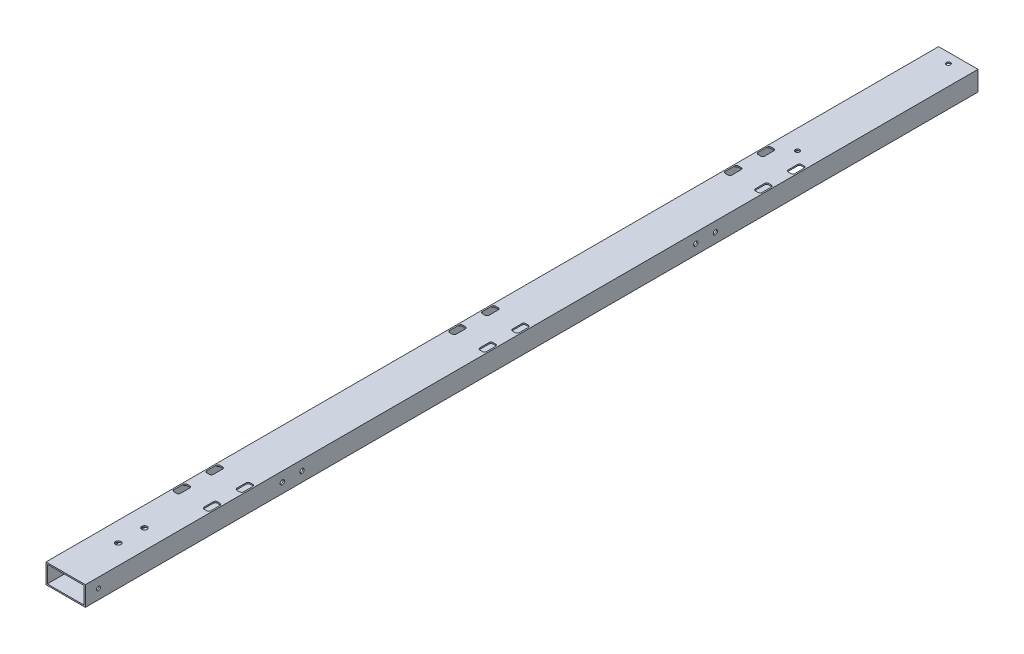
SolidWorks part; units mm, degrees
material "1060 合金"
ref_plane "前视基准面" through (0, 0, 0) normal (0, 0, 1) x (1, 0, 0)
ref_plane "上视基准面" through (0, 0, 0) normal (0, 1, 0) x (1, 0, 0)
ref_plane "右视基准面" through (0, 0, 0) normal (1, 0, 0) x (0, 0, -1)
other "Configuration Table"
sketch "草图1" plane through (0, 0, 0) normal (0, 0, 1) x (1, 0, 0)
  line L1 (0, 0) -> (30, 0)
  line L2 (0, 0) -> (0, -15)
  line L3 (0, -15) -> (30, -15)
  line L4 (30, 0) -> (30, -15)
  dimension "D1" = 15
  dimension "D2" = 30
extrude "拉伸-薄壁1" add sketch "草图1" along normal blind 800 thin thin type one direction reverse wall 1
sketch "草图2" plane through (0, -15, 0) normal (0, -1, 0) x (1, 0, 0)
  circle A1 centre (7.5, 825) radius 2.6
  circle A2 centre (7.5, 825) radius 2.6
  dimension "D1" = 0
extrude "切除-拉伸1" [suppressed] cut sketch "草图2" against normal up to next
sketch "草图3" plane through (0, 0, 0) normal (-1, 0, 0) x (0, 0, 1)
  line L0 (800, 0) -> (0, 0) construction
  line L1 (0, 0) -> (0, -15) construction
  circle A0 centre (215, -7.5) radius 1.7
  circle A1 centre (170, -7.5) radius 1.7
  dimension "D1" = 3.4
  dimension "D2" = 3.4
  dimension "D3" = 45
  dimension "D4" = 7.5
  dimension "D5" = 7.5
  dimension "D6" = 170
sketch "草图4" plane through (30, 0, 0) normal (1, 0, 0) x (0, 0, -1)
  line L0 (-800, -15) -> (0, -15) construction
  line L1 (-800, -15) -> (-800, 0) construction
  circle A0 centre (-790, -7.5) radius 1.5
  dimension "D1" = 3
  dimension "D2" = 7.5
  dimension "D3" = 10
extrude "切除-拉伸3" cut sketch "草图4" against normal through all
sketch "草图5" plane through (30, 0, 0) normal (1, 0, 0) x (0, 0, -1)
  line L0 (-800, 0) -> (0, 0) construction
  line L1 (0, -15) -> (0, 0) construction
  line L2 (-800, -1) -> (-800, -14) construction
  circle A0 centre (-320, -7.5) radius 1.65
  circle A1 centre (-335, -7.5) radius 1.65
  circle A2 centre (-635, -7.5) radius 1.65
  circle A3 centre (-650, -7.5) radius 1.65
  dimension "D1" = 3.3
  dimension "D4" = 3.3
  dimension "D7" = 7.5
  dimension "D9" = 3.3
  dimension "D10" = 3.3
  dimension "D2" = 7.5
  dimension "D3" = 15
  dimension "D5" = 7.5
  dimension "D6" = 320
  dimension "D8" = 7.5
  dimension "D11" = 15
  dimension "D12" = 150
extrude "切除-拉伸4" cut sketch "草图5" against normal through all
sketch "草图6" plane through (0, 0, 0) normal (0, 0, -1) x (-1, 0, 0)
  line L4 (0, -15) -> (0, 0)
  line L5 (0, 0) -> (-30, 0)
  line L6 (-30, 0) -> (-30, -15)
  line L7 (-30, -15) -> (0, -15)
  line L8 (0, -15) -> (0, 0)
  line L9 (0, 0) -> (-30, 0)
  line L10 (-30, 0) -> (-30, -15)
  line L11 (-30, -15) -> (0, -15)
  dimension "D1" = 0
extrude "切除-拉伸5" cut sketch "草图6" against normal blind 300
sketch "草图7" [suppressed] plane through (0, 0, 0) normal (0, 1, 0) x (1, 0, 0)
  line L0 (15, -300) -> (15, -861.2957) construction
  line L1 (0, -300) -> (30, -300) construction
  line L2 (0, -550) -> (263.5539, -550) construction
  line L3 (0, -800) -> (0, -300) construction
  circle A0 centre (7.5, -545) radius 1.25
  circle A1 centre (22.5, -545) radius 1.25
  circle A2 centre (22.5, -555) radius 1.25
  circle A3 centre (7.5, -555) radius 1.25
  circle A4 centre (7.5, -405) radius 1.25
  circle A5 centre (22.5, -405) radius 1.25
  circle A6 centre (22.5, -415) radius 1.25
  circle A7 centre (7.5, -415) radius 1.25
  circle A8 centre (7.5, -685) radius 1.25
  circle A9 centre (22.5, -685) radius 1.25
  circle A10 centre (22.5, -695) radius 1.25
  circle A11 centre (7.5, -695) radius 1.25
  circle A12 centre (7.5, -545) radius 1.25
  circle A13 centre (22.5, -545) radius 1.25
  circle A14 centre (22.5, -555) radius 1.25
  circle A15 centre (7.5, -555) radius 1.25
  line M12 (0, -300) -> (0, -800)
  line M14 (30, -800) -> (30, -300)
  dimension "D1" = 2.5
  dimension "D3" = 15
  dimension "D4" = 10
  dimension "D2" = 250
  dimension "D6" = 135
  dimension "D5" = 2
extrude "切除-拉伸6" [suppressed] cut sketch "草图7" against normal blind 155 contours A4 M12 | A7 M12 | A5 M14 | A6 M14 | A1 M14 | A0 M12 | A2 M14 | A8 M12 | A11 M12 | A9 M14 | A10 M14 | A3
sketch "草图8" plane through (0, 0, 300) normal (0, 0, -1) x (-1, 0, 0)
  line L0 (-1, -14) -> (-1, -1) construction
  line L1 (-1, -1) -> (-29, -1) construction
  line L2 (-29, -1) -> (-29, -14) construction
  line L3 (-29, -14) -> (-1, -14) construction
  line L4 (-30, -15) -> (0, -15)
  line L5 (0, -15) -> (0, 0)
  line L6 (0, 0) -> (-30, 0)
  line L7 (-30, 0) -> (-30, -15)
  line L8 (-30, -15) -> (0, -15)
  line L9 (0, -15) -> (0, 0)
  line L10 (0, 0) -> (-30, 0)
  line L11 (-30, 0) -> (-30, -15)
  line L12 (-1, -14) -> (-1, -1)
  line L13 (-1, -1) -> (-29, -1)
  line L14 (-29, -1) -> (-29, -14)
  line L15 (-29, -14) -> (-1, -14)
  dimension "D1" = 0
extrude "凸台-拉伸1" add sketch "草图8" along normal blind 180
sketch "草图9" plane through (0, 0, 0) normal (0, 1, 0) x (1, 0, 0)
  line L0 (0, -800) -> (0, -120) construction
  line L1 (30, -800) -> (0, -800) construction
  circle A0 centre (15, -740) radius 2.05
  circle A1 centre (15, -760) radius 2.05
  dimension "D1" = 4.1
  dimension "D2" = 15
  dimension "D3" = 60
  dimension "D4" = 2
extrude "切除-拉伸7" cut sketch "草图9" against normal blind 10
sketch "草图10" plane through (0, -15, 0) normal (0, -1, 0) x (1, 0, 0)
  line L0 (15, 735) -> (15, 760) construction
  line L1 (8, 735) -> (8, 760)
  line L2 (22, 735) -> (22, 760)
  line L3 (0, 800) -> (0, 120) construction
  line L4 (0, 800) -> (30, 800) construction
  arc A0 (8, 735) -> (22, 735) centre (15, 735) ccw
  arc A1 (22, 760) -> (8, 760) centre (15, 760) ccw
  point P2 (15, 747.5)
  dimension "D3" = 7
  dimension "D1" = 25
  dimension "D2" = 15
  dimension "D4" = 40
extrude "切除-拉伸8" cut sketch "草图10" against normal blind 10
sketch "草图11" plane through (0, -15, 0) normal (0, -1, 0) x (1, 0, 0)
  line L0 (0, 800) -> (0, 120) construction
  line L1 (30, 120) -> (0, 120) construction
  circle A0 centre (15, 127.5) radius 1.6
  circle A1 centre (15, 242.5) radius 1.6
  dimension "D1" = 3.2
  dimension "D2" = 15
  dimension "D3" = 7.5
  dimension "D4" = 2
extrude "切除-拉伸9" cut sketch "草图11" against normal through all
sketch "草图12" plane through (0, -15, 0) normal (0, -1, 0) x (1, 0, 0)
  line L0 (15, 247) -> (15, 237) construction
  line L1 (22, 247) -> (22, 237)
  line L2 (8, 247) -> (8, 237)
  line L3 (30, 120) -> (0, 120) construction
  line L4 (30, 800) -> (30, 120) construction
  arc A0 (22, 247) -> (8, 247) centre (15, 247) ccw
  arc A1 (8, 237) -> (22, 237) centre (15, 237) ccw
  point P2 (15, 242)
  dimension "D1" = 7
  dimension "D2" = 117
  dimension "D3" = 10
  dimension "D4" = 15
extrude "切除-拉伸10" cut sketch "草图12" against normal up to next
sketch "草图13" plane through (0, -15, 0) normal (0, -1, 0) x (1, 0, 0)
  line L0 (30, 800) -> (30, 120) construction
  line L1 (0, 800) -> (30, 800) construction
  circle A0 centre (27.5, 700) radius 1.25
  circle A1 centre (2.5, 700) radius 1.25
  circle A2 centre (2.5, 675) radius 1.25
  circle A3 centre (27.5, 675) radius 1.25
  circle A4 centre (27.5, 465) radius 1.25
  circle A5 centre (27.5, 490) radius 1.25
  circle A6 centre (2.5, 490) radius 1.25
  circle A7 centre (2.5, 465) radius 1.25
  circle A8 centre (27.5, 255) radius 1.25
  circle A9 centre (27.5, 280) radius 1.25
  circle A10 centre (2.5, 280) radius 1.25
  circle A11 centre (2.5, 255) radius 1.25
  dimension "D1" = 2.5
  dimension "D2" = 2.5
  dimension "D3" = 100
  dimension "D4" = 2
  dimension "D5" = 2
  dimension "D6" = 3
extrude "切除-拉伸11" cut sketch "草图13" against normal through all
sketch "草图14" plane through (0, -15, 0) normal (0, -1, 0) x (1, 0, 0)
  line L0 (30, 800) -> (30, 120) construction
  line L1 (1, 705) -> (6, 705)
  line L2 (1, 705) -> (1, 695)
  line L3 (1, 670) -> (6, 670)
  line L4 (29, 705) -> (29, 695)
  line L5 (0, 800) -> (0, 120) construction
  line L6 (1, 495) -> (6, 495)
  line L7 (1, 695) -> (6, 695)
  line L8 (1, 695) -> (1, 705)
  line L9 (1, 705) -> (6, 705)
  line L10 (6, 695) -> (6, 705)
  line L11 (29, 705) -> (24, 705)
  line L12 (29, 705) -> (29, 695)
  line L13 (29, 695) -> (24, 695)
  line L14 (24, 705) -> (24, 695)
  line L15 (1, 680) -> (6, 680)
  line L16 (1, 680) -> (1, 670)
  line L17 (1, 670) -> (6, 670)
  line L18 (6, 680) -> (6, 670)
  line L19 (29, 670) -> (24, 670)
  line L20 (29, 670) -> (29, 680)
  line L21 (29, 680) -> (24, 680)
  line L22 (24, 670) -> (24, 680)
  line L23 (1, 495) -> (1, 485)
  line L24 (1, 460) -> (6, 460)
  line L25 (29, 495) -> (29, 485)
  line L26 (1, 485) -> (6, 485)
  line L27 (1, 485) -> (1, 495)
  line L28 (1, 495) -> (6, 495)
  line L29 (6, 485) -> (6, 495)
  line L30 (29, 495) -> (24, 495)
  line L31 (29, 495) -> (29, 485)
  line L32 (29, 485) -> (24, 485)
  line L33 (24, 495) -> (24, 485)
  line L34 (1, 470) -> (6, 470)
  line L35 (1, 470) -> (1, 460)
  line L36 (1, 460) -> (6, 460)
  line L37 (6, 470) -> (6, 460)
  line L38 (29, 460) -> (24, 460)
  line L39 (29, 460) -> (29, 470)
  line L40 (29, 470) -> (24, 470)
  line L41 (24, 460) -> (24, 470)
  line L42 (1, 285) -> (6, 285)
  line L43 (1, 285) -> (1, 275)
  line L44 (1, 250) -> (6, 250)
  line L45 (29, 285) -> (29, 275)
  line L46 (1, 275) -> (6, 275)
  line L47 (1, 275) -> (1, 285)
  line L48 (1, 285) -> (6, 285)
  line L49 (6, 275) -> (6, 285)
  line L50 (29, 285) -> (24, 285)
  line L51 (29, 285) -> (29, 275)
  line L52 (29, 275) -> (24, 275)
  line L53 (24, 285) -> (24, 275)
  line L54 (1, 260) -> (6, 260)
  line L55 (1, 260) -> (1, 250)
  line L56 (1, 250) -> (6, 250)
  line L57 (6, 260) -> (6, 250)
  line L58 (29, 250) -> (24, 250)
  line L59 (29, 250) -> (29, 260)
  line L60 (29, 260) -> (24, 260)
  line L61 (24, 250) -> (24, 260)
  line L62 (24, 670) -> (29, 670)
  line L63 (29, 680) -> (29, 670)
  line L64 (1, 680) -> (1, 670)
  line L65 (24, 705) -> (29, 705)
  line L66 (24, 460) -> (29, 460)
  line L67 (24, 495) -> (29, 495)
  line L68 (1, 470) -> (1, 460)
  line L69 (29, 470) -> (29, 460)
  line L70 (24, 285) -> (29, 285)
  line L71 (1, 260) -> (1, 250)
  line L72 (29, 260) -> (29, 250)
  line L73 (24, 250) -> (29, 250)
  circle A0 centre (27.5, 700) radius 1.25 construction
  circle A1 centre (27.5, 675) radius 1.25 construction
  circle M5 centre (27.5, 280) radius 1.25
  circle M6 centre (27.5, 465) radius 1.25
  circle M7 centre (2.5, 465) radius 1.25
  circle M8 centre (2.5, 490) radius 1.25
  circle M9 centre (27.5, 490) radius 1.25
  circle M10 centre (27.5, 675) radius 1.25
  circle M11 centre (2.5, 675) radius 1.25
  circle M12 centre (2.5, 700) radius 1.25
  circle M13 centre (2.5, 280) radius 1.25
  circle M14 centre (2.5, 255) radius 1.25
  circle M15 centre (27.5, 255) radius 1.25
  circle M16 centre (27.5, 700) radius 1.25
  dimension "D1" = 5
  dimension "D2" = 5
  dimension "D3" = 1
  dimension "D4" = 1
  dimension "D5" = 10
  dimension "D6" = 5
  dimension "D7" = 10
  dimension "D8" = 5
  dimension "D9" = 5
  dimension "D10" = 10
  dimension "D11" = 5
  dimension "D12" = 10
  dimension "D13" = 3
extrude "切除-拉伸13" cut sketch "草图14" against normal blind 10 from offset 10 contours L18 L15 L16 L3 M11 | L22 L19 L20 L21 M10 | L11 L14 L13 L4 M16 | L7 L10 L1 L2 M12 | L26 L29 L6 L23 M8 | L30 L33 L32 L25 M9 | L37 L34 L35 L24 M7 | L41 L38 L39 L40 M6 | L50 L53 L52 L45 M5 | L61 L58 L59 L60 M15 | L57 L54 L55 L44 M14 | L46 L49 L42 L43 M13 region at (3.5, -15, 704.8882) region at (1.1118, -15, 675) region at (28.8882, -15, 700) region at (3.5, -15, 494.8882) region at (26.5, -15, 670.1118) region at (1.1118, -15, 465) region at (28.8882, -15, 490) region at (26.5, -15, 460.1118) region at (3.5, -15, 284.8882) region at (1.1118, -15, 255) region at (28.8882, -15, 280) region at (26.5, -15, 250.1118) offset against normal yes
fillet "圆角2" radius 1.5 48 edges at (6, -0.5, 470) (1, -0.5, 470) (1, -0.5, 460) (6, -0.5, 460) (24, -0.5, 670) (29, -0.5, 670) (29, -0.5, 680) (24, -0.5, 680) (6, -0.5, 260) (1, -0.5, 260) (1, -0.5, 250) (6, -0.5, 250) (6, -0.5, 285) (1, -0.5, 275) (6, -0.5, 275) (6, -0.5, 680) (1, -0.5, 680) (1, -0.5, 670) (6, -0.5, 670) (24, -0.5, 250) (29, -0.5, 250) (29, -0.5, 260) (24, -0.5, 260) (24, -0.5, 695) (29, -0.5, 695) (29, -0.5, 705) (24, -0.5, 705) (6, -0.5, 705) (1, -0.5, 705) (1, -0.5, 695) (6, -0.5, 695) (6, -0.5, 495) (1, -0.5, 495) (1, -0.5, 485) (6, -0.5, 485) (24, -0.5, 275) (29, -0.5, 275) (29, -0.5, 285) (24, -0.5, 285) (24, -0.5, 460) (29, -0.5, 460) (29, -0.5, 470) (24, -0.5, 470) (24, -0.5, 485) (29, -0.5, 485) (29, -0.5, 495) (24, -0.5, 495) (1, -0.5, 285)
